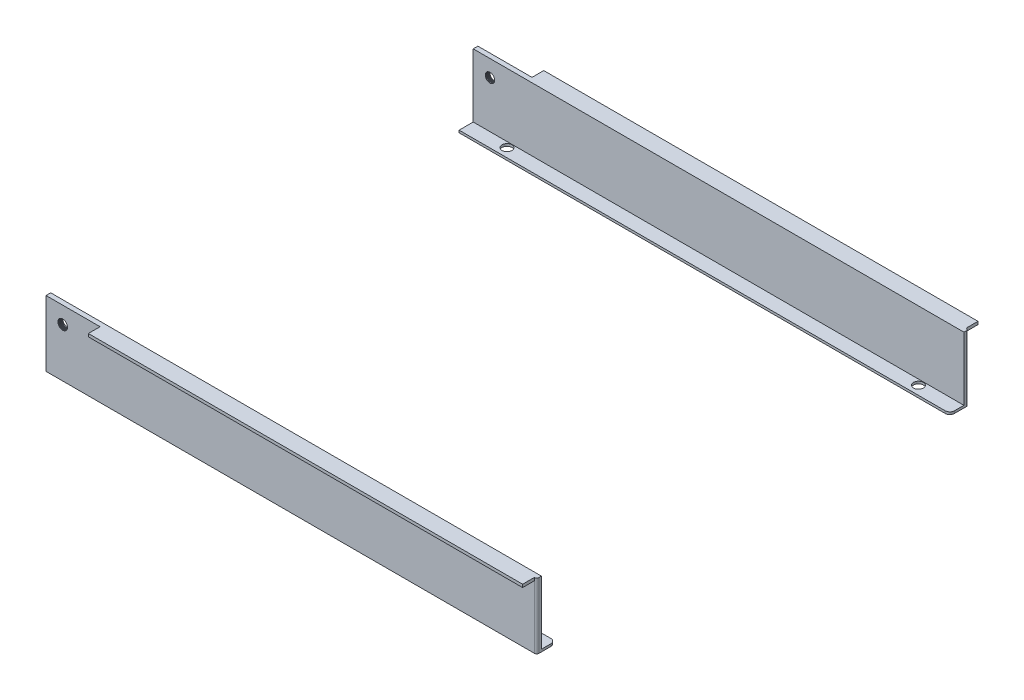
SolidWorks part; units mm, degrees
ref_plane "前基準面" through (0, 0, 0) normal (0, 0, 1) x (1, 0, 0)
ref_plane "上基準面" through (0, 0, 0) normal (0, 1, 0) x (1, 0, 0)
ref_plane "右基準面" through (0, 0, 0) normal (1, 0, 0) x (0, 0, -1)
sketch "草圖1" plane through (0, 0, 0) normal (0, 0, 1) x (1, 0, 0)
  line L1 (-115, 15) -> (115, 15)
  line L2 (-115, 15) -> (-115, -15)
  line L3 (-115, -15) -> (115, -15)
  line L4 (115, 15) -> (115, -15)
  line L5 (0, -15) -> (0, 15) construction
  line L6 (-115, 0) -> (115, 0) construction
  point P0 (0, 0)
  dimension "D1" = 30
  dimension "D2" = 230
extrude "填料-伸長1" add sketch "草圖1" along normal blind 2
sketch "草圖2" plane through (0, 0, 2) normal (0, 0, 1) x (1, 0, 0)
  line L1 (115, 15) -> (-115, 15) construction
  line L2 (115, -15) -> (115, 15) construction
  line L3 (-68, 15) -> (115, 15)
  line L4 (-68, 15) -> (-68, 14)
  line L5 (-68, 14) -> (115, 14)
  line L6 (115, 15) -> (115, 14)
extrude "填料-伸長2" add sketch "草圖2" along normal blind 5
fillet "圓角1" radius 2 1 edges at (-68, 14.5, 7)
fillet "圓角2" radius 2 1 edges at (115, 14.5, 7)
sketch "草圖3" plane through (0, 0, 0) normal (0, 0, -1) x (-1, 0, 0)
  line L0 (115, 15) -> (115, -15) construction
  line L1 (-115, -15) -> (115, -15)
  line L2 (-115, -15) -> (-115, -14.0001)
  line L3 (-115, -14.0001) -> (115, -14.0001)
  line L4 (115, -15) -> (115, -14.0001)
extrude "填料-伸長3" add sketch "草圖3" along normal blind 6
fillet "圓角3" radius 2 1 edges at (-115, -14.5001, -6)
fillet "圓角4" radius 2 1 edges at (115, -14.5001, -6)
sketch "草圖4" plane through (0, 0, 2) normal (0, 0, 1) x (1, 0, 0)
  circle A0 centre (-86.9057, 5.9156) radius 2
extrude "除料-伸長1" cut sketch "草圖4" against normal blind 6
thread "螺紋1" pitch 0.3175 start angle 0, offset 0, length 10, pitch 0.5, diameter 4
ref_plane "平面1" through (-84.9057, 5.9156, 0) normal (0, -1, 0) x (1, 0, 0)
sketch "螺紋輪廓1" plane through (-84.9057, 5.9156, 0) normal (0, -1, 0) x (1, 0, 0)
  line L0 (0, 0) -> (0, 0.3175) construction
  line L1 (0, 0) -> (0.2, 0.1155)
  line L2 (0.2, 0.1155) -> (0.2, 0.1552)
  line L3 (0.2, 0.1552) -> (0, 0.2706)
  line L4 (0.2, 0.1353) -> (0, 0.1353) construction
  line L11 (0, 0) -> (0, 0.2706)
  point P2 (0, 0)
  dimension "Pitch" = 0.3175
  dimension "Profile_Angle" = 60
  dimension "Profile_Land" = 0.0397
  dimension "Profile_Height" = 0.2
fillet "圓角5" radius 2 1 edges at (-115, 15, 1)
fillet "圓角6" radius 1 3 edges at (1, 15, 0) (-114.4142, 14.4142, 0) (-115, -0.5001, 0)
fillet "圓角7" radius 1 1 edges at (115, -0.5, 2)
sketch "草圖6" plane through (0, 0, 7) normal (0, 0, 1) x (1, 0, 0)
  line L1 (-118.3014, 16.7729) -> (-94.0415, 16.7729)
  line L2 (-118.3014, 16.7729) -> (-118.3014, -19.6953)
  line L3 (-118.3014, -19.6953) -> (-94.0415, -19.6953)
  line L4 (-94.0415, 16.7729) -> (-94.0415, -19.6953)
extrude "除料-伸長5" cut sketch "草圖6" against normal blind 15
sketch "草圖7" plane through (0, -15, 0) normal (0, -1, 0) x (1, 0, 0)
  circle A0 centre (-77.3987, -2.2601) radius 2.1
  circle A1 centre (97.9009, -2.2601) radius 2.1
extrude "除料-伸長6" cut sketch "草圖7" against normal blind 10
sketch "草圖8" plane through (115, 0, 0) normal (1, 0, 0) x (0, 0, -1)
  line L0 (0, -14.0001) -> (0, 14) construction
  line L1 (-7, 15) -> (0, 15)
  line L2 (-7, 15) -> (-7, 13)
  line L3 (-7, 13) -> (0, 13)
  line L4 (0, 15) -> (0, 13)
extrude "除料-伸長8" cut sketch "草圖8" against normal blind 218
sketch "草圖9" plane through (0, 0, 2) normal (0, 0, 1) x (1, 0, 0)
  line L1 (114, 13) -> (-71, 13)
  line L2 (114, 13) -> (114, 11.76)
  line L3 (114, 11.76) -> (-71, 11.76)
  line L4 (-71, 13) -> (-71, 11.76)
extrude "填料-伸長4" add sketch "草圖9" along normal blind 5
ref_plane "平面2" through (0, 0, -90) normal (0, 0, -1) x (-1, 0, 0)
mirror "鏡射3" about plane through (0, 0, -90) normal (0, 0, -1) of bodies 113
